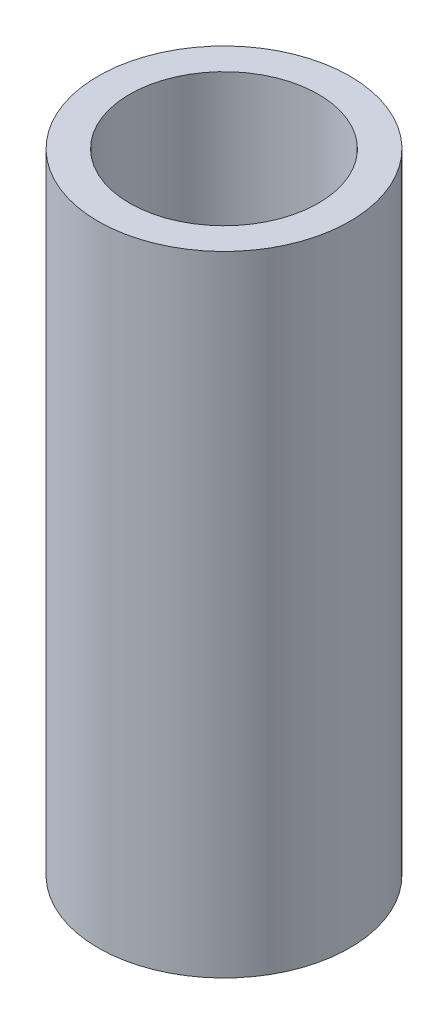
SolidWorks part; units mm, degrees
ref_plane "Front Plane" through (0, 0, 0) normal (0, 0, 1) x (1, 0, 0)
ref_plane "Top Plane" through (0, 0, 0) normal (0, 1, 0) x (1, 0, 0)
ref_plane "Right Plane" through (0, 0, 0) normal (1, 0, 0) x (0, 0, -1)
sketch "Sketch1" plane through (0, 0, 0) normal (0, 1, 0) x (1, 0, 0)
  circle A0 centre (0, 0) radius 3
  dimension "D1" = 6
extrude "Boss-Extrude1" add sketch "Sketch1" along normal blind 15
sketch "Sketch2" plane through (0, 15, 0) normal (0, 1, 0) x (1, 0, 0)
  circle A0 centre (0, 0) radius 2.25
  dimension "D1" = 4.5
extrude "Cut-Extrude1" cut sketch "Sketch2" against normal through all
